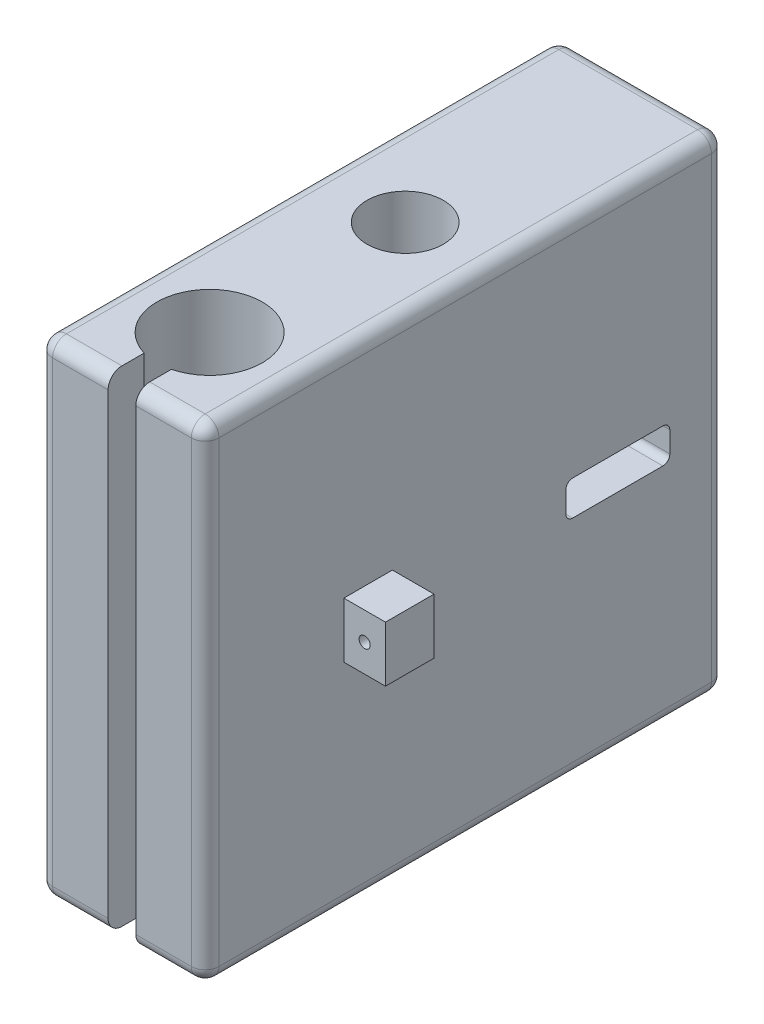
SolidWorks part; units mm, degrees
ref_plane "Front Plane" through (0, 0, 0) normal (0, 0, 1) x (1, 0, 0)
ref_plane "Top Plane" through (0, 0, 0) normal (0, 1, 0) x (1, 0, 0)
ref_plane "Right Plane" through (0, 0, 0) normal (1, 0, 0) x (0, 0, -1)
ref_plane "Plano1" through (-220, 0, 0) normal (1, 0, 0) x (0, 0, -1)
sketch "Esboço1" plane through (-220, 0, 0) normal (1, 0, 0) x (0, 0, -1)
  line L0 (-460.4999, 246.154) -> (-460.4999, 230.354) construction
  line L1 (-465.4999, 248.254) -> (-390.4999, 248.254)
  line L2 (-465.4999, 248.254) -> (-465.4999, 178.254)
  line L3 (-465.4999, 178.254) -> (-390.4999, 178.254)
  line L4 (-390.4999, 248.254) -> (-390.4999, 178.254)
  dimension "D1" = 75
  dimension "D2" = 70
  dimension "D3" = 5
extrude "Ressalto-extrusão1" add sketch "Esboço1" along normal blind 12 and the other way blind 12
sketch "Esboço3" plane through (0, 248.254, 0) normal (0, 1, 0) x (1, 0, 0)
  line L5 (-232, -465.4999) -> (-208, -465.4999) construction
  line L7 (-220, -465.4999) -> (-218, -465.4999)
  line L10 (-218, -465.4999) -> (-218, -460.3692)
  line L11 (-220, -465.4999) -> (-222, -465.4999)
  line L14 (-222, -465.4999) -> (-222, -460.292)
  arc A3 (-218, -460.3692) -> (-222, -460.292) centre (-219.8586, -452.9999) ccw
  circle A8 centre (-219.5085, -425.1499) radius 5.5
  circle A9 centre (-219.5085, -425.1499) radius 5.5
  dimension "D1" = 15.2
  dimension "D3" = 2
  dimension "D4" = 2
  dimension "D2" = 0.5
extrude "Corte-extrusão1" cut sketch "Esboço3" against normal through all
sketch "Esboço4" plane through (0, 0, 390.4999) normal (0, 0, -1) x (-1, 0, 0)
  line L0 (220, 248.254) -> (220, 178.254) construction
  line L1 (232, 248.254) -> (208, 248.254) construction
  line L2 (232, 178.254) -> (208, 178.254) construction
  circle A0 centre (219.8586, 238.254) radius 4.1
  circle A1 centre (219.8586, 188.254) radius 4.1
  dimension "D1" = 8.2
  dimension "D2" = 8.2
extrude "Corte-extrusão2" cut sketch "Esboço4" against normal blind 20
fillet "Filete1" radius 2 14 edges at (-227, 178.254, 465.4999) (-213, 178.254, 465.4999) (-213, 248.254, 465.4999) (-227, 248.254, 465.4999) (-208, 178.254, 427.9999) (-208, 248.254, 427.9999) (-208, 213.254, 465.4999) (-232, 178.254, 427.9999) (-232, 213.254, 465.4999) (-232, 248.254, 427.9999) (-220, 248.254, 390.4999) (-220, 178.254, 390.4999) (-208, 213.254, 390.4999) (-232, 213.254, 390.4999)
sketch "Esboço5" plane through (0, 0, 390.4999) normal (0, 0, -1) x (-1, 0, 0)
  line L8 (213.995, 195.2586) -> (225.995, 195.2488)
  line L9 (225.995, 195.2488) -> (226.0245, 231.2487)
  line L10 (226.0245, 231.2487) -> (214.0245, 231.2586)
  line L11 (214.0245, 231.2586) -> (213.995, 195.2586)
  line L12 (213.995, 195.2586) -> (225.995, 195.2488)
  line L13 (225.995, 195.2488) -> (226.0245, 231.2487)
  line L14 (226.0245, 231.2487) -> (214.0245, 231.2586)
  line L15 (214.0245, 231.2586) -> (213.995, 195.2586)
  dimension "D1" = 0
extrude "Corte-extrusão3" cut sketch "Esboço5" against normal blind 29
sketch "Esboço6" plane through (-232, 0, 0) normal (-1, 0, 0) x (0, 0, 1)
  line L0 (392.4999, 213.254) -> (463.4999, 213.254) construction
  line L1 (392.4999, 246.254) -> (392.4999, 180.254) construction
  line L2 (463.4999, 180.254) -> (463.4999, 246.254) construction
  line L3 (398.4999, 213.254) -> (413.4999, 213.254) construction
  line L4 (399.4999, 215.754) -> (412.4999, 215.754)
  line L5 (398.4999, 214.754) -> (398.4999, 211.754)
  line L6 (399.4999, 210.754) -> (412.4999, 210.754)
  line L7 (413.4999, 214.754) -> (413.4999, 211.754)
  arc A0 (412.4999, 215.754) -> (413.4999, 214.754) centre (412.4999, 214.754) cw
  arc A1 (412.4999, 210.754) -> (413.4999, 211.754) centre (412.4999, 211.754) ccw
  arc A2 (398.4999, 211.754) -> (399.4999, 210.754) centre (399.4999, 211.754) ccw
  arc A3 (399.4999, 215.754) -> (398.4999, 214.754) centre (399.4999, 214.754) ccw
  point P14 (413.4999, 215.754)
  point P17 (413.4999, 210.754)
  point P22 (398.4999, 215.754)
  dimension "D4" = 1
  dimension "D1" = 5
  dimension "D2" = 15
  dimension "D3" = 6
extrude "Corte-extrusão4" cut sketch "Esboço6" against normal blind 28
sketch "Esboço7" plane through (-208, 0, 0) normal (1, 0, 0) x (0, 0, -1)
  line L0 (-463.4999, 246.254) -> (-463.4999, 180.254) construction
  line L1 (-445.4999, 217.254) -> (-438.4999, 217.254)
  line L2 (-445.4999, 217.254) -> (-445.4999, 209.254)
  line L3 (-445.4999, 209.254) -> (-438.4999, 209.254)
  line L4 (-438.4999, 217.254) -> (-438.4999, 209.254)
  line L5 (-465.4999, 180.254) -> (-465.4999, 246.254) construction
  point P6 (-463.4999, 213.254)
  point P7 (-445.4999, 213.254)
  dimension "D1" = 7
  dimension "D2" = 8
  dimension "D3" = 20
extrude "Ressalto-extrusão2" add sketch "Esboço7" along normal blind 6 and the other way blind 30
ref_point "Ponto1"
sketch "Esboço9" plane through (0, 0, 445.4999) normal (0, 0, 1) x (1, 0, 0)
  line L0 (-205, 217.254) -> (-205, 209.254) construction
  line L3 (-208, 217.254) -> (-202, 217.254) construction
  line L6 (-208, 209.254) -> (-202, 209.254) construction
  line L7 (-208, 213.254) -> (-202, 213.254) construction
  line L8 (-208, 246.254) -> (-208, 180.254) construction
  line L9 (-202, 217.254) -> (-202, 209.254) construction
hole_wizard "Broca de rosquear para tarraxa de M2x0.41" positions "Esboço13" profile "Esboço14" hole size "M2x0.4" standard "Ansi Metric" end condition through all
sketch "Esboço13" plane through (0, 0, 445.4999) normal (0, 0, 1) x (1, 0, 0)
  line L0 (-205, 217.254) -> (-205, 209.254) construction
  point P0 (-205, 213.254)
sketch "Esboço14" plane through (-205, 213.254, 445.4999) normal (1, 0, 0) x (0, -1, 0)
  line L0 (0, 0) -> (0, 55)
  line L1 (0, 55) -> (0.8, 55)
  line L2 (0.8, 55) -> (0.8, 0)
  line L5 (0.8, 0) -> (0, 0)
  line L11 (0, -6.35) -> (0, 107.95) construction
  dimension "Thru Hole Dia." = 1.6
  dimension "Thru Hole Depth" = 55
sketch "Esboço15" plane through (0, 0, 445.4999) normal (0, 0, 1) x (1, 0, 0)
  line L0 (-235, 217.254) -> (-235, 209.254) construction
  line L1 (-238, 217.254) -> (-232, 217.254) construction
  line L2 (-238, 209.254) -> (-232, 209.254) construction
  line L3 (-238, 213.254) -> (-232, 213.254) construction
  line L4 (-238, 217.254) -> (-238, 209.254) construction
  line L5 (-232, 180.254) -> (-232, 246.254) construction
hole_wizard "Broca de rosquear para tarraxa de M2x0.42" positions "Esboço16" profile "Esboço17" hole size "M2x0.4" standard "Ansi Metric" end condition through all
sketch "Esboço16" plane through (0, 0, 445.4999) normal (0, 0, 1) x (1, 0, 0)
  line L0 (-235, 217.254) -> (-235, 209.254) construction
  point P0 (-235, 213.254)
sketch "Esboço17" plane through (-235, 213.254, 445.4999) normal (1, 0, 0) x (0, -1, 0)
  line L0 (0, 0) -> (0, 55)
  line L1 (0, 55) -> (0.8, 55)
  line L2 (0.8, 55) -> (0.8, 0)
  line L5 (0.8, 0) -> (0, 0)
  line L11 (0, -6.35) -> (0, 107.95) construction
  dimension "Thru Hole Dia." = 1.6
  dimension "Thru Hole Depth" = 55
